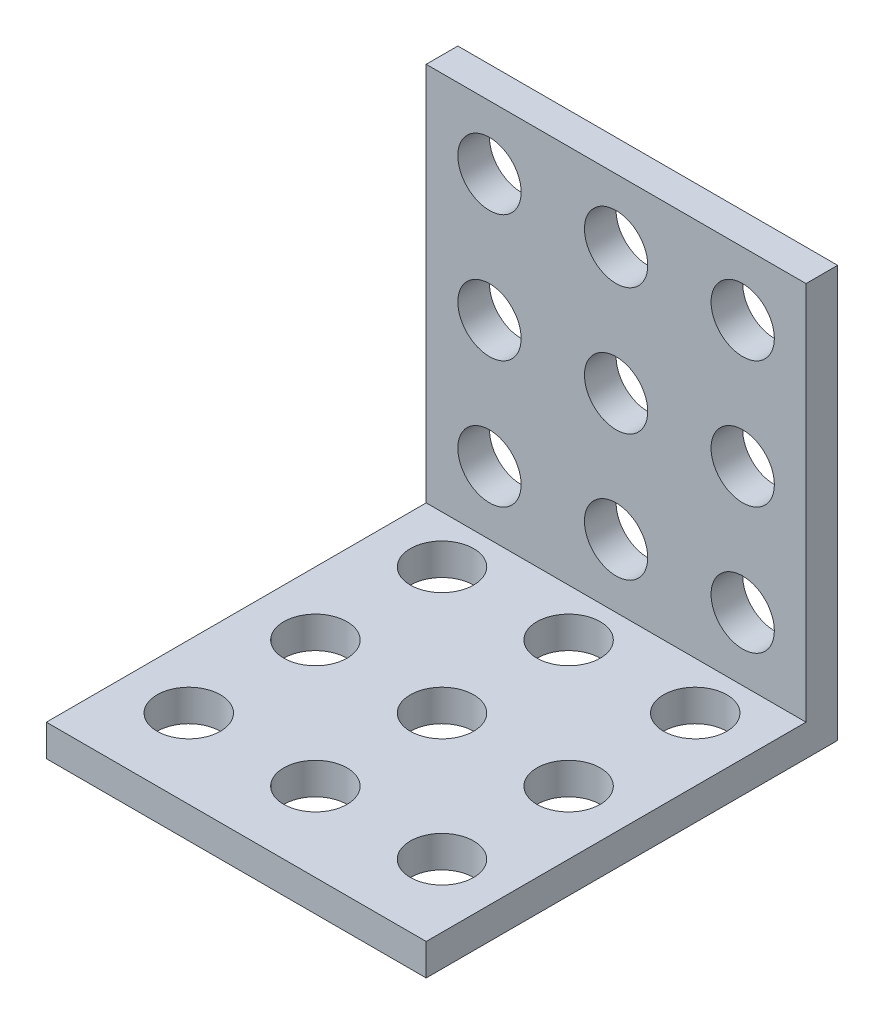
SolidWorks part; units mm, degrees
material "6061 Alloy"
ref_plane "前视基准面" through (0, 0, 0) normal (0, 0, 1) x (1, 0, 0)
ref_plane "上视基准面" through (0, 0, 0) normal (0, 1, 0) x (1, 0, 0)
ref_plane "右视基准面" through (0, 0, 0) normal (1, 0, 0) x (0, 0, -1)
other "Configuration Table"
sketch "Sketch1" plane through (0, 0, 0) normal (0, 1, 0) x (1, 0, 0)
  line L0 (-12, 13) -> (-12, -13)
  line L5 (12, -13) -> (-12, -13)
  line L6 (12, -13) -> (12, 13)
  line L7 (12, 13) -> (-12, 13)
  line L8 (-12, -13) -> (-12, 13)
  line L9 (12, -13) -> (-12, 13) construction
  line L10 (-12, 0) -> (12, 0) construction
  line L11 (-12, 11) -> (12, 11)
  circle A8 centre (0, 0) radius 2
  circle A9 centre (-8, 0) radius 2
  circle A10 centre (8, 0) radius 2
  circle A11 centre (-8, 8) radius 2
  circle A13 centre (8, 8) radius 2
  circle A14 centre (0, 8) radius 2
  circle A15 centre (8, -8) radius 2
  circle A16 centre (0, -8) radius 2
  circle A17 centre (-8, -8) radius 2
  point P0 (0, 0)
  dimension "D4" = 8
  dimension "D6" = 8
  dimension "D1" = 26
  dimension "D2" = 24
  dimension "D3" = 2
  dimension "D5" = 8
extrude "Boss-Extrude1" add sketch "Sketch1" along normal blind 2 contours L11 L8 L5 L6 A16 A8 A9 A10 A11 A13 A14 A15 A17 region at (0, 0, -10.6606)
extrude "Boss-Extrude2" add sketch "Sketch1<3>" along normal blind 26 contours L0 L11 L6 L7 region at (0, 0, -12)
sketch "Sketch1<3>" plane through (0, 0, 0) normal (0, 1, 0) x (1, 0, 0) same geometry as "Sketch1"
sketch "Sketch2" plane through (0, 0, -11) normal (0, 0, 1) x (1, 0, 0)
  line L0 (-12, 26) -> (12, 26) construction
  line L1 (-12, 26) -> (-12, 2) construction
  line L2 (-12, 14) -> (12, 14) construction
  line L3 (12, 26) -> (12, 2) construction
  circle A1 centre (-8, 22) radius 2
  circle A2 centre (0, 22) radius 2
  circle A3 centre (8, 22) radius 2
  circle A4 centre (-8, 14) radius 2
  circle A5 centre (0, 14) radius 2
  circle A6 centre (8, 14) radius 2
  circle A7 centre (8, 6) radius 2
  circle A8 centre (0, 6) radius 2
  circle A9 centre (-8, 6) radius 2
  dimension "D1" = 4
  dimension "D3" = 8
  dimension "D5" = 8
  dimension "D2" = 4
  dimension "D4" = 8
extrude "Cut-Extrude1" cut sketch "Sketch2" against normal blind 26
